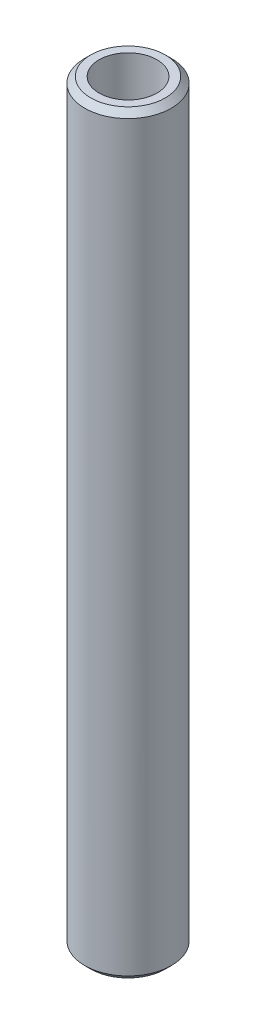
SolidWorks part; units mm, degrees
ref_plane "Front Plane" through (0, 0, 0) normal (0, 0, 1) x (1, 0, 0)
ref_plane "Top Plane" through (0, 0, 0) normal (0, 1, 0) x (1, 0, 0)
ref_plane "Right Plane" through (0, 0, 0) normal (1, 0, 0) x (0, 0, -1)
sketch "Sketch1" plane through (0, 0, 0) normal (0, 1, 0) x (1, 0, 0)
  circle A0 centre (0, 0) radius 25
  dimension "SHAFT_OD" = 50
extrude "Boss-Extrude1" add sketch "Sketch1" along normal blind 435.9504
sketch "Sketch2" plane through (0, 0, 0) normal (0, 1, 0) x (1, 0, 0)
  circle A0 centre (0, 0) radius 16.7166
  dimension "BORE_D" = 33.4332
extrude "Cut-Extrude1" cut sketch "Sketch2" along normal through all
chamfer "Chamfer1" distance 3.4508 angle 45 2 edges at (0, 435.9504, 25) (0, 0, 25)
